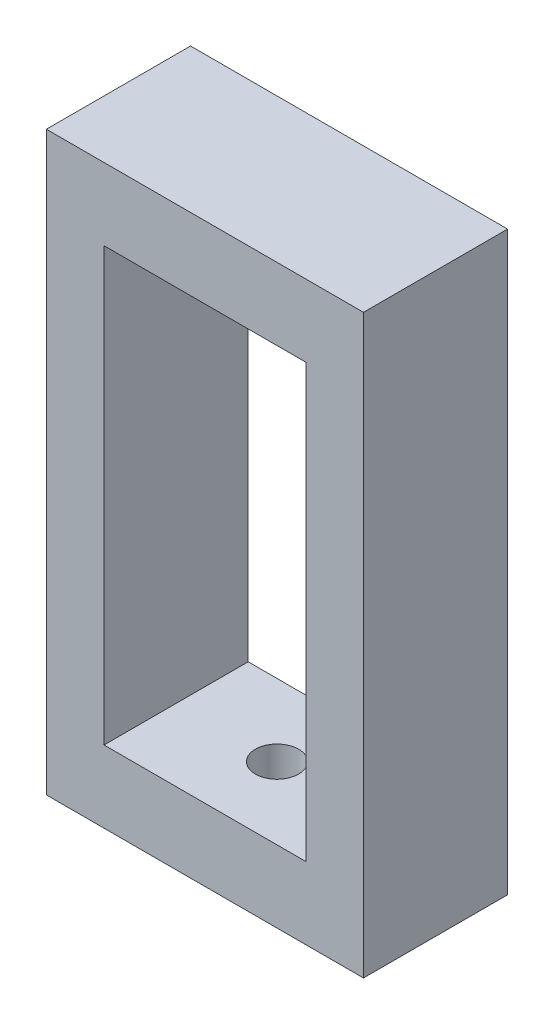
SolidWorks part; units mm, degrees
material "Brass"
ref_plane "Front Plane" through (0, 0, 0) normal (0, 0, 1) x (1, 0, 0)
ref_plane "Top Plane" through (0, 0, 0) normal (0, 1, 0) x (1, 0, 0)
ref_plane "Right Plane" through (0, 0, 0) normal (1, 0, 0) x (0, 0, -1)
sketch "Sketch1" plane through (0, 0, 0) normal (0, 0, 1) x (1, 0, 0)
  line L0 (0, 0) -> (22, 0)
  line L1 (22, 0) -> (22, 40)
  line L2 (22, 40) -> (0, 40)
  line L3 (0, 40) -> (0, 0)
  line L4 (4, 5) -> (18, 5)
  line L5 (18, 5) -> (18, 35)
  line L6 (18, 35) -> (4, 35)
  line L7 (4, 35) -> (4, 5)
extrude "Boss-Extrude1" add sketch "Sketch1" along normal blind 10
sketch "Sketch2" plane through (0, 0, 0) normal (0, 1, 0) x (1, 0, 0)
  circle A0 centre (11, -5) radius 1.5
  dimension "D1" = 3
extrude "Cut-Extrude1" cut sketch "Sketch2" against normal mid plane 30
